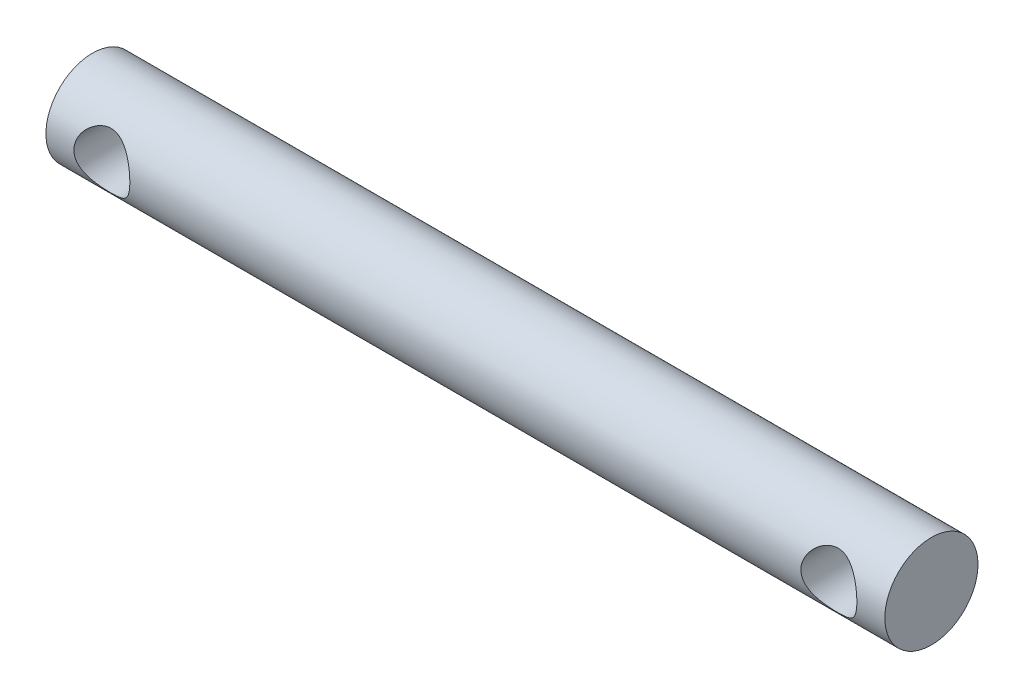
SolidWorks part; units mm, degrees
material "6061 Alloy"
ref_plane "Front Plane" through (0, 0, 0) normal (0, 0, 1) x (1, 0, 0)
ref_plane "Top Plane" through (0, 0, 0) normal (0, 1, 0) x (1, 0, 0)
ref_plane "Right Plane" through (0, 0, 0) normal (1, 0, 0) x (0, 0, -1)
sketch "Sketch1" plane through (0, 0, 0) normal (1, 0, 0) x (0, 0, -1)
  circle A0 centre (0, 0) radius 2.5
  dimension "D1" = 5
extrude "Boss-Extrude1" add sketch "Sketch1" along normal mid plane 45
sketch "Sketch2" plane through (0, 0, 0) normal (0, 0, 1) x (1, 0, 0)
  line L0 (2.75, 0) -> (-2.75, 0) construction
  line L1 (-22.5, 2.5) -> (-22.5, -2.5) construction
  line L2 (22.5, -2.5) -> (22.5, 2.5) construction
  circle A0 centre (-19.5, 0) radius 1.5
  circle A1 centre (19.5, 0) radius 1.5
  dimension "D1" = 3
  dimension "D2" = 3
  dimension "D3" = 3
extrude "Cut-Extrude1" cut sketch "Sketch2" against normal mid plane 30
